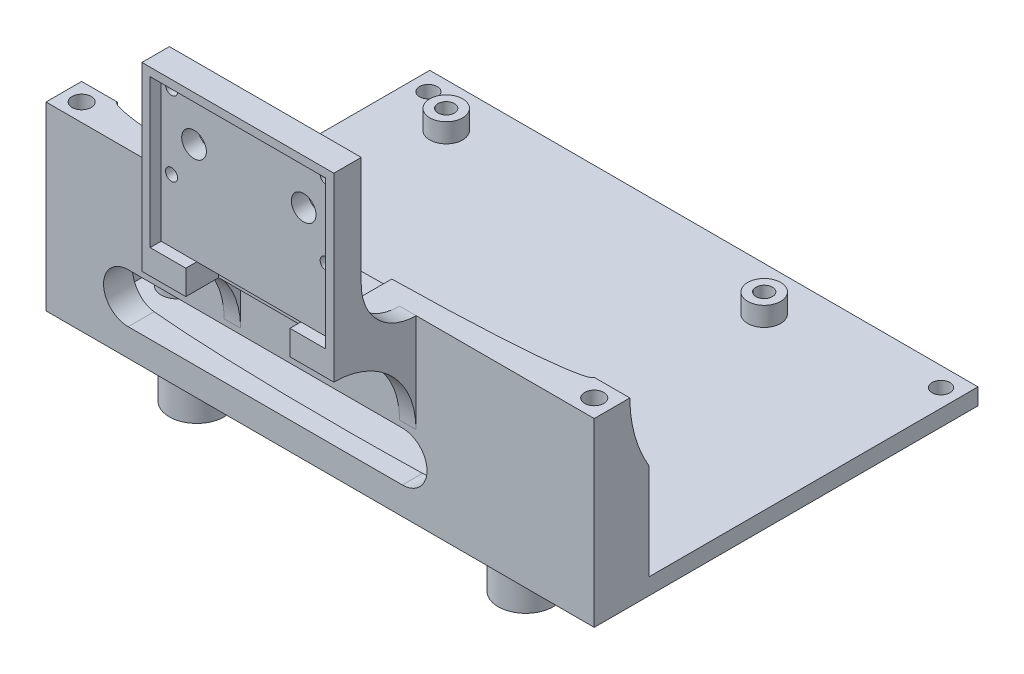
SolidWorks part; units mm, degrees
ref_plane "Front Plane" through (0, 0, 0) normal (0, 0, 1) x (1, 0, 0)
ref_plane "Top Plane" through (0, 0, 0) normal (0, 1, 0) x (1, 0, 0)
ref_plane "Right Plane" through (0, 0, 0) normal (1, 0, 0) x (0, 0, -1)
sketch "Sketch1" plane through (0, 0, 0) normal (0, 1, 0) x (1, 0, 0)
  line L0 (-64.9136, 0) -> (58.8496, 0) construction
  line L1 (-50, 37.5) -> (50, 37.5)
  line L2 (-50, 37.5) -> (-50, -37.5)
  line L3 (-50, -37.5) -> (50, -37.5)
  line L4 (50, 37.5) -> (50, -37.5)
  line L5 (-50, 32.5) -> (50, 32.5)
  circle A0 centre (-39, 24.5) radius 1.5
  circle A3 centre (19, 24.5) radius 1.5
  circle A5 centre (19, -24.5) radius 1.5
  circle A6 centre (-39, -24.5) radius 1.5
  point P4 (50, 0)
  point P5 (0, 37.5)
  dimension "D3" = 3
  dimension "D6" = 3
  dimension "D1" = 100
  dimension "D2" = 75
  dimension "D4" = 11
  dimension "D5" = 13
  dimension "D7" = 31
  dimension "D8" = 5
extrude "Boss-Extrude1" add sketch "Sketch1" along normal blind 3 contours L2 L0 L4 L5 A0 A3 | L0 L2 L3 L4 A5 A6 region at (0.0437, 0, -16.214) region at (0.0378, 0, 18.7282)
sketch "Sketch2" plane through (0, 3, 0) normal (0, 1, 0) x (1, 0, 0)
  line L0 (-50, 32.5) -> (-50, -37.5) construction
  line L1 (-50, 7.5) -> (-43.5, 7.5)
  line L3 (-50, -37.5) -> (50, -37.5)
  line L4 (-43.5, 7.5) -> (-43.5, -31)
  line L6 (-43.5, -31) -> (43.5, -31)
  line L7 (-50, 7.5) -> (-50, -37.5)
  line L9 (50, 7.5) -> (50, -37.5)
  line L10 (43.5, 7.5) -> (50, 7.5)
  line L11 (43.5, 7.5) -> (43.5, -31)
  line L13 (50, 7.5) -> (50, -37.5)
  line M9 (-50, 32.5) -> (-50, -37.5)
  line M10 (-50, -37.5) -> (50, -37.5)
  line M11 (50, -37.5) -> (50, 32.5)
  dimension "D1" = 6.5
  dimension "D2" = 6.5
  dimension "D3" = 6.5
  dimension "D4" = 45
extrude "Boss-Extrude2" add sketch "Sketch2" along normal blind 30 contours L10 L11 L6 L4 L1 M9 M10 M11 region at (-46.75, 3, -6.4034)
sketch "Sketch3" plane through (50, 0, 0) normal (1, 0, 0) x (0, 0, -1)
  line L0 (-31, 33) -> (-31, 0) construction
  line L1 (-37.5, 33) -> (7.5, 33) construction
  line L2 (32.5, 0) -> (-37.5, 0) construction
  line L3 (-37.5, 33) -> (-37.5, 0) construction
  line L5 (-27.5, 20.5021) -> (7.5, 20.5021)
  line L6 (-27.5, 20.5021) -> (-27.5, 3)
  line L7 (-27.5, 3) -> (7.5, 3)
  line L8 (7.5, 20.5021) -> (7.5, 3)
  ellipse E0 centre (7.5, 33) end of major axis (46, 33) minor radius 30 (7.5, 3) -> (-31, 33) cw
  line M6 (7.5, 3) -> (7.5, 33)
  line M7 (7.5, 33) -> (-37.5, 33)
  dimension "D1" = 6.5
  dimension "D2" = 10
extrude "Cut-Extrude1" cut sketch "Sketch3" against normal up to next and the other way through all contours E0 L5 M6 M7 | E0 L5 M6 | L7 E0 L6 region at (50, 26.8477, 11.1921) region at (50, 7.8185, 19.3376) region at (50, 13.2901, 6.3457)
extrude "Cut-Extrude2" cut sketch "Sketch3<3>" against normal up to surface (100 mm away) contours E0 L5 M6 M7 | E0 L5 M6 region at (50, 26.8477, 11.1921) region at (50, 13.2901, 6.3457) up to face at (-50, 12, -0.8333)
sketch "Sketch3<3>" plane through (50, 0, 0) normal (1, 0, 0) x (0, 0, -1) same geometry as "Sketch3"
sketch "Sketch4" plane through (0, 0, 37.5) normal (0, 0, 1) x (1, 0, 0)
  line L0 (-35, 9.5) -> (15, 9.5) construction
  line L1 (-35, 14) -> (15, 14)
  line L2 (-35, 5) -> (15, 5)
  line L4 (-50, 0) -> (50, 0) construction
  line L5 (-50, 33) -> (-50, 0) construction
  arc A0 (-35, 14) -> (-35, 5) centre (-35, 9.5) ccw
  arc A1 (15, 5) -> (15, 14) centre (15, 9.5) ccw
  point P2 (-10, 9.5)
  point P7 (-15.6225, 9.5)
  point P8 (-21.9457, 9.5)
  point P11 (0, 0)
  point P12 (-31.3, 9.5)
  point P13 (-22.1519, 17.7533)
  point P14 (-33.2175, 9.5)
  point P15 (-10.9488, 9.5)
  point P16 (-35.0044, 9.5)
  point P17 (-36.7227, 9.5)
  dimension "D2" = 4.5
  dimension "D1" = 40
  dimension "D3" = 50
  dimension "D4" = 9.5
extrude "Cut-Extrude3" cut sketch "Sketch4" against normal up to next
sketch "Sketch6" plane through (0, 33, 0) normal (0, 1, 0) x (1, 0, 0)
  line L0 (-50, -34.25) -> (50, -34.25) construction
  line L1 (-50, -31) -> (-50, -37.5) construction
  line L2 (50, -37.5) -> (50, -31) construction
  line L3 (-46.75, 7.5) -> (-46.75, -37.5) construction
  line L4 (-50, 7.5) -> (-43.5, 7.5) construction
  line L5 (-50, -37.5) -> (50, -37.5) construction
  line L6 (46.75, -27.5) -> (46.75, -37.5) construction
  line L7 (50, -27.5) -> (43.5, -27.5) construction
  circle A0 centre (-46.75, -34.25) radius 1.75
  circle A1 centre (46.75, -34.25) radius 1.75
  dimension "D1" = 3.5
extrude "Cut-Extrude4" cut sketch "Sketch6" against normal blind 10
sketch "Sketch8" plane through (0, 33, 0) normal (0, 1, 0) x (1, 0, 0)
  line L0 (-43.5, -31) -> (43.5, -31) construction
  line L1 (-43.5, -31) -> (43.5, -31)
  ellipse E0 centre (0, -31) end of major axis (-43.5, -31) minor radius 3 (-43.5, -31) -> (43.5, -31) ccw
  dimension "D1" = 3
extrude "Cut-Extrude5" cut sketch "Sketch8" against normal up to surface (30 mm away) up to face at (-0.4062, 3, 2.2188)
sketch "Sketch9" plane through (0, 0, 0) normal (0, -1, 0) x (1, 0, 0)
  line L0 (-30, 2.5) -> (30, 2.5) construction
  line L1 (-30, 30) -> (30, 30) construction
  line L2 (-30, 30) -> (-30, -25) construction
  line L3 (-30, -25) -> (30, -25) construction
  line L4 (30, 30) -> (30, -25) construction
  line L5 (0, 30) -> (0, -25) construction
  circle A0 centre (-30, 30) radius 5
  circle A3 centre (-30, -25) radius 5
  circle A4 centre (30, -25) radius 5
  circle A5 centre (30, 30) radius 5
  point P4 (0, 30)
  dimension "D3" = 10
  dimension "D1" = 55
  dimension "D2" = 60
  dimension "D4" = 30
extrude "Boss-Extrude3" add sketch "Sketch9" along normal blind 8
sketch "Sketch10" plane through (0, -8, 0) normal (0, -1, 0) x (1, 0, 0)
  line L0 (0, 30) -> (0, -25) construction
  line L1 (-30, 30) -> (30, 30) construction
  line L2 (-30, 30) -> (-30, -25) construction
  line L3 (-30, -25) -> (30, -25) construction
  line L4 (30, 30) -> (30, -25) construction
  line L5 (-30, 2.5) -> (30, 2.5) construction
  circle A0 centre (-30, 30) radius 2.5
  circle A1 centre (-30, -25) radius 2.5
  circle A2 centre (30, -25) radius 2.5
  circle A3 centre (30, 30) radius 2.5
  dimension "D1" = 5
extrude "Cut-Extrude6" cut sketch "Sketch10" against normal blind 6.5
sketch "Sketch11" plane through (0, 3, 0) normal (0, 1, 0) x (1, 0, 0)
  line L0 (46.75, -34.25) -> (46.75, 32.5) construction
  line L1 (-50, 32.5) -> (50, 32.5) construction
  line L2 (-46.75, -34.25) -> (-46.75, 32.5) construction
  line L3 (-50, 29) -> (50, 29) construction
  line L4 (-50, 32.5) -> (-50, 7.5) construction
  line L5 (50, 32.5) -> (50, -27.5) construction
  circle A0 centre (46.75, 29) radius 1.625
  circle A1 centre (-46.75, 29) radius 1.625
  dimension "D2" = 3.25
  dimension "D3" = 3.25
  dimension "D1" = 3.5
extrude "Cut-Extrude7" cut sketch "Sketch11" against normal through all
sketch "Sketch19" plane through (0, 3, 0) normal (0, 1, 0) x (1, 0, 0)
  circle A0 centre (-39, -24.5) radius 3
  circle A1 centre (19, -24.5) radius 3
  circle A2 centre (19, 24.5) radius 3
  circle A3 centre (-39, 24.5) radius 3
  circle A4 centre (-39, 24.5) radius 1.5 construction
  circle A5 centre (-39, 24.5) radius 1.5
  circle A6 centre (19, 24.5) radius 1.5 construction
  circle A7 centre (19, 24.5) radius 1.5
  circle A8 centre (-39, -24.5) radius 1.5 construction
  circle A9 centre (-39, -24.5) radius 1.5
  circle A10 centre (19, -24.5) radius 1.5 construction
  circle A11 centre (19, -24.5) radius 1.5
  dimension "D1" = 6
extrude "Boss-Extrude5" add sketch "Sketch19" along normal blind 3.5
sketch "Sketch20" plane through (-50, 0, 0) normal (-1, 0, 0) x (0, 0, 1)
  line L0 (-32.5, 3) -> (7.5, 3)
  line L2 (7.5, 3) -> (7.5, 5.3706)
  ellipse E1 centre (-7.5, 33) end of major axis (31, 33) minor radius 30 (-7.5, 3) -> (31, 33) ccw construction
  ellipse E2 centre (-7.5, 33) end of major axis (31, 33) minor radius 30 (-7.5, 3) -> (7.5, 5.3706) ccw
  point P15 (17.5422, 10.2135)
  ellipse M3 centre (-7.5, 33) end of major axis (31, 33) minor radius 30 (31, 33) -> (-7.5, 3) cw
  dimension "D1" = 40
extrude "Cut-Extrude12" cut sketch "Sketch20" against normal up to next contours L0 L2 M3 region at (-50, 3.7061, 3.7803)
sketch "Sketch12" plane through (0, 0, 0) normal (1, 0, 0) x (0, 0, -1)
  line L0 (-37.5, 33) -> (-37.5, 0) construction
  line L4 (-37.5, 33) -> (-37.5, 15)
  line L5 (-52.5, 33) -> (-52.5, 30)
  line L8 (-52.5, 33) -> (-37.5, 33)
  line L9 (-52.5, 31.5) -> (-37.5, 31.5) construction
  line L11 (-52.5, 63) -> (-47.5, 63)
  line L12 (-52.5, 63) -> (-52.5, 33)
  line L13 (-52.5, 33) -> (-47.5, 33)
  line L14 (-47.5, 63) -> (-47.5, 33)
  arc A0 (-37.5, 15) -> (-52.5, 30) centre (-52.5, 15) ccw
  arc A1 (-37.5, 33) -> (-47.5, 43) centre (-37.5, 43) cw
  dimension "D1" = 15
  dimension "D3" = 3
  dimension "D2" = 15
  dimension "D5" = 90
  dimension "D6" = 5
  dimension "D4" = 30
extrude "Boss-Extrude4" add sketch "Sketch12" along normal mid plane 35 contours L9 L5 A0 L4 | L5 L9 L4 L8 | L8 A1 L14 | L12 L13 L14 L11 region at (0, 32.25, 45) region at (0, 35.2337, 45.2663) region at (0, 27.9529, 42.1695)
sketch "Sketch13" plane through (0, 33, 0) normal (0, 1, 0) x (1, 0, 0)
  line L0 (-17.5, -37.5) -> (17.5, -37.5) construction
  line L2 (-14.5, -37.5) -> (14.5, -37.5)
  line L3 (-14.5, -37.5) -> (-14.5, -52.5)
  line L4 (-14.5, -52.5) -> (14.5, -52.5)
  line L5 (14.5, -37.5) -> (14.5, -52.5)
  line L7 (0, -52.5) -> (0, -34) construction
  line L9 (17.5, -52.5) -> (-17.5, -52.5) construction
  ellipse E0 centre (0, -31) end of major axis (43.5, -31) minor radius 3 (-43.5, -31) -> (43.5, -31) ccw construction
  ellipse E1 centre (0, -31) end of major axis (43.5, -31) minor radius 3 (-43.5, -31) -> (43.5, -31) ccw construction
  point P8 (0, 0)
  point P9 (0, -34)
  point P13 (0, -52.5)
  dimension "D1" = 3
extrude "Cut-Extrude8" cut sketch "Sketch13" against normal up to vertex (18 mm away) from offset 3 up to point (17.5, 15, 37.5) offset against normal yes
sketch "Sketch16" plane through (0, 0, 52.5) normal (0, 0, 1) x (1, 0, 0)
  line L1 (-16, 61.5) -> (16, 61.5)
  line L2 (-16, 61.5) -> (-16, 34.5)
  line L3 (-16, 34.5) -> (16, 34.5)
  line L4 (16, 61.5) -> (16, 34.5)
  line L5 (0, 63) -> (0, 30) construction
  line L6 (17.5, 63) -> (-17.5, 63) construction
  line L7 (-14.5, 30) -> (14.5, 30) construction
  point P12 (0, 61.5)
  dimension "D1" = 27
  dimension "D2" = 32
  dimension "D3" = 4.5
extrude "Cut-Extrude9" cut sketch "Sketch16" against normal blind 2
sketch "Sketch17" plane through (0, 33, 0) normal (0, 1, 0) x (1, 0, 0)
  line L0 (0, -34) -> (0, -52.5) construction
  line L1 (17.5, -52.5) -> (-17.5, -52.5) construction
  line L2 (17.5, -37.5) -> (-17.5, -37.5) construction
  line L3 (-14.5, -37.5) -> (14.5, -37.5)
  line L4 (-14.5, -37.5) -> (-14.5, -47.5)
  line L5 (-14.5, -47.5) -> (14.5, -47.5)
  line L6 (14.5, -37.5) -> (14.5, -47.5)
  line L7 (17.5, -47.5) -> (-17.5, -47.5) construction
  line L8 (-17.5, -37.5) -> (-17.5, -47.5) construction
  ellipse E0 centre (0, -31) end of major axis (43.5, -31) minor radius 3 (-43.5, -31) -> (43.5, -31) ccw construction
  point P15 (0, -37.5)
  point P16 (0, -34)
  point P17 (0, -34)
  dimension "D1" = 3
extrude "Cut-Extrude10" cut sketch "Sketch17" along normal up to vertex (30 mm away) up to point (17.5, 63, 47.5)
sketch "Sketch18" plane through (0, 0, 50.5) normal (0, 0, 1) x (1, 0, 0)
  line L0 (-8, 33) -> (8, 33) construction
  line L1 (-8, 34.5) -> (8, 34.5)
  line L2 (-8, 31.5) -> (8, 31.5)
  line L3 (-16, 34.5) -> (16, 34.5) construction
  line L4 (-15.2, 59.6) -> (15.2, 59.6) construction
  line L5 (-16, 61.5) -> (16, 61.5) construction
  line L6 (-16, 61.5) -> (-16, 34.5) construction
  line L7 (-16, 34.5) -> (16, 34.5) construction
  line L8 (0, 61.5) -> (0, 33) construction
  line L9 (16, 61.5) -> (-16, 61.5) construction
  line L11 (-9.5, 33) -> (-9.5, 34.5)
  line L12 (-9.5, 34.5) -> (-8, 34.5)
  line L13 (9.5, 33) -> (9.5, 34.5)
  line L14 (9.5, 34.5) -> (8, 34.5)
  line L15 (16, 61.5) -> (16, 34.5) construction
  line L16 (14.1, 59.6) -> (14.1, 46) construction
  line L17 (10, 52.8) -> (-10, 52.8) construction
  line L18 (-16, 48) -> (16, 48) construction
  line L19 (-16, 61.5) -> (-16, 34.5) construction
  line L20 (16, 34.5) -> (16, 61.5) construction
  arc A0 (-8, 34.5) -> (-8, 31.5) centre (-8, 33) ccw
  arc A1 (8, 31.5) -> (8, 34.5) centre (8, 33) ccw
  circle A6 centre (14.1, 59.6) radius 1.1
  circle A7 centre (14.1, 46) radius 1.1
  circle A8 centre (-14.1, 59.6) radius 1.1
  circle A9 centre (-14.1, 46) radius 1.1
  circle A10 centre (-10, 52.8) radius 2.25
  circle A11 centre (10, 52.8) radius 2.25
  point P2 (0, 33)
  point P11 (0, 34.5)
  point P18 (0, 34.5)
  point P34 (16, 48)
  point P47 (0, 59.6)
  point P51 (0, 52.8)
  point P54 (14.1, 52.8)
  line M8 (-16, 34.5) -> (16, 34.5)
  dimension "D2" = 1.5
  dimension "D3" = 1.9
  dimension "D4" = 13.6
  dimension "D5" = 28.2
  dimension "D10" = 2.2
  dimension "D15" = 4.5
  dimension "D1" = 16
  dimension "D8" = 32
  dimension "D9" = 27
  dimension "D14" = 20
extrude "Cut-Extrude11" cut sketch "Sketch18" against normal through all both and the other way through all contours A1 A0 L2 M8 | A0 L11 M8 | A1 L13 M8 | A8 | A10 | A9 | A7 | A11 | A6 region at (-9.1649, 34.1649, 50.5) region at (0, 33, 50.5) region at (9.1649, 34.1649, 50.5) region at (14.1, 46, 50.5) region at (-14.1, 59.6, 50.5) region at (-14.1, 46, 50.5) region at (-10, 52.8, 50.5) region at (10, 52.8, 50.5)
sketch "Sketch21" plane through (0, 0, 52.5) normal (0, 0, 1) x (1, 0, 0)
  line L0 (14.5, 30) -> (-14.5, 30) construction
  line L1 (-9.5, 34.5) -> (9.5, 34.5)
  line L2 (-9.5, 34.5) -> (-9.5, 30)
  line L3 (-9.5, 30) -> (9.5, 30)
  line L4 (9.5, 34.5) -> (9.5, 30)
  point P7 (9.5, 34.5)
extrude "Cut-Extrude13" cut sketch "Sketch21" against normal blind 6
equation "\"D2@Sketch12\"=\"D1@Sketch12\""
